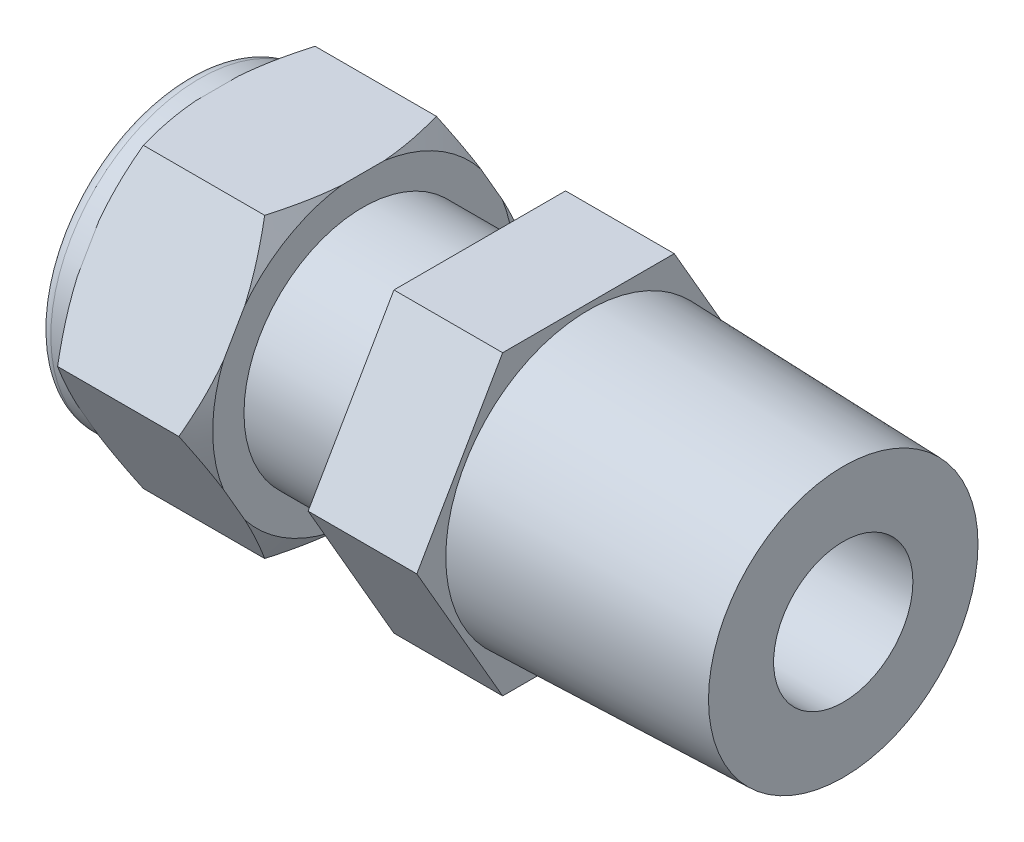
SolidWorks part; units mm, degrees
ref_plane "Front" through (0, 0, 0) normal (0, 0, 1) x (1, 0, 0)
ref_plane "Top" through (0, 0, 0) normal (0, 1, 0) x (1, 0, 0)
ref_plane "Right" through (0, 0, 0) normal (1, 0, 0) x (0, 0, -1)
sketch "BodySch" plane through (0, 0, 0) normal (0, 0, 1) x (1, 0, 0)
  line L0 (-103.6847, 0) -> (134.0726, 0) construction
  line L1 (-49.022, 0) -> (-49.022, 11.1125)
  line L2 (-49.022, 11.1125) -> (-41.3766, 11.1125)
  line L3 (-41.3766, 11.1125) -> (-41.3766, 8.89)
  line L4 (-41.3766, 8.89) -> (-27.178, 8.89)
  line L5 (-27.178, 8.89) -> (-27.178, 10.668)
  line L6 (-27.178, 10.668) -> (-19.05, 10.668)
  line L8 (-19.05, 10.668) -> (0, 10.0749)
  line L9 (0, 10.0749) -> (0, 0)
  line L14 (0, 0) -> (-49.022, 0)
  dimension "Dia_ouside_D1" = 22.225
  dimension "Dia_inside" = 17.78
  dimension "Dia_outside_D" = 21.336
  dimension "D4" = 1.783
  dimension "Length" = 49.022
  dimension "L4" = 19.05
  dimension "C" = 21.844
  dimension "Hex1_middle_point" = 7.6454
revolve "Body" add sketch "BodySch" angle 360 about L0
sketch "Hex1Sch_G" plane through (-41.3766, 0, 0) normal (1, 0, 0) x (0, 0, -1)
  line L1 (12.8316, 0) -> (6.4158, 11.1125)
  line L2 (6.4158, 11.1125) -> (-6.4158, 11.1125)
  line L3 (-6.4158, 11.1125) -> (-12.8316, 0)
  line L4 (-12.8316, 0) -> (-6.4158, -11.1125)
  line L5 (-6.4158, -11.1125) -> (6.4158, -11.1125)
  line L6 (6.4158, -11.1125) -> (12.8316, 0)
  circle A0 centre (0, 0) radius 11.1125 construction
  dimension "G" = 22.225
extrude "Hex1" add sketch "Hex1Sch_G" along normal mid plane 10.922
sketch "PlaneCSch" plane through (0, 0, 0) normal (0, 0, 1) x (1, 0, 0)
  line L0 (-27.178, 10.668) -> (-27.178, -10.668) construction
  point P0 (-27.178, 5.1403)
ref_plane "PlaneC" through (-27.178, 0, 0) normal (-1, 0, 0) x (0, 0, 1)
sketch "Hex2Sch_F" plane through (-27.178, 0, 0) normal (-1, 0, 0) x (0, 0, 1)
  line L3 (12.8316, 0) -> (6.4158, 11.1125)
  line L5 (6.4158, 11.1125) -> (-6.4158, 11.1125)
  line L7 (-6.4158, 11.1125) -> (-12.8316, 0)
  line L9 (-12.8316, 0) -> (-6.4158, -11.1125)
  line L11 (-6.4158, -11.1125) -> (6.4158, -11.1125)
  line L12 (6.4158, -11.1125) -> (12.8316, 0)
  circle A2 centre (0, 0) radius 11.1125 construction
  dimension "F" = 22.225
extrude "Hex2" add sketch "Hex2Sch_F" against normal blind 8.128
sketch "HexfilletSch" plane through (0, 0, 0) normal (0, 1, 0) x (1, 0, 0)
  line L0 (-46.8376, 11.2277) -> (-45.9116, 12.8316)
  line L1 (-46.8376, 12.8316) -> (-46.8376, 9.6237) construction
  line L2 (-35.9156, 12.8316) -> (-46.8376, 12.8316) construction
  line L3 (-35.9156, 12.8316) -> (-35.9156, 6.4158) construction
  line L5 (-35.9156, 11.2277) -> (-36.8416, 12.8316)
  line L6 (-46.8376, 11.2277) -> (-46.8376, 12.8316)
  line L7 (-35.9156, 11.2277) -> (-35.9156, 12.8316)
  line L8 (-46.8376, 12.8316) -> (-45.9116, 12.8316)
  line L9 (-41.9948, 0) -> (5.5242, 0) construction
  line L10 (-103.6847, 0) -> (134.0726, 0) construction
  line L12 (-35.9156, 12.8316) -> (-36.8416, 12.8316)
  dimension "D1" = 60
  dimension "D2" = 30
fillet "BodyFillet" radius 0.889 1 edges at (-49.022, 0, 11.1125)
revolve "Hexfillet" cut sketch "HexfilletSch" angle 360 about L9
sketch "DSch" plane through (-49.022, 0, 0) normal (1, 0, 0) x (0, 0, -1)
  circle A0 centre (0, 0) radius 6.35
  dimension "T" = 12.7
extrude "Cut-ExtrudeD" cut sketch "DSch" along normal blind 22.86
sketch "E" plane through (0, 0, 0) normal (1, 0, 0) x (0, 0, -1)
  circle A0 centre (0, 0) radius 5.207
  dimension "E" = 10.414
extrude "Cut-ExtrudeE" cut sketch "E" against normal up to surface (26.162 mm away) up to face at (-26.162, 0, -6.35)
sketch "Sketch1" plane through (0, 0, 0) normal (0, 1, 0) x (1, 0, 0)
  line L0 (0, -5.207) -> (0, 5.207) construction
  line L1 (-19.05, -10.668) -> (-19.05, 10.668) construction
  line L2 (-26.162, 5.207) -> (-26.162, -5.207) construction
  point P0 (0, 0)
  point P4 (-19.05, 0)
  point P7 (-26.162, 0)
other "RPoint1"
other "CPoint2" parameters "Diameter"=12.7, "StubLength"=0
ref_axis "Axis2" through (-36.162, 0, 0) along (1, 0, 0)
equation "\"Hex1_middle_point@BodySch\"=\"C@BodySch\"*.35"
equation "\"Depth@Hex1\"=\"C@BodySch\"*.5"
equation "\"Depth@Hex2\"=\"Length@BodySch\"-\"L4@BodySch\"-\"C@BodySch\""
equation "\"Dia_ouside_D1@BodySch\"=\"G@Hex1Sch_G\""
equation "\"D1@BodyFillet\"=\"Dia_ouside_D1@BodySch\"/25"
